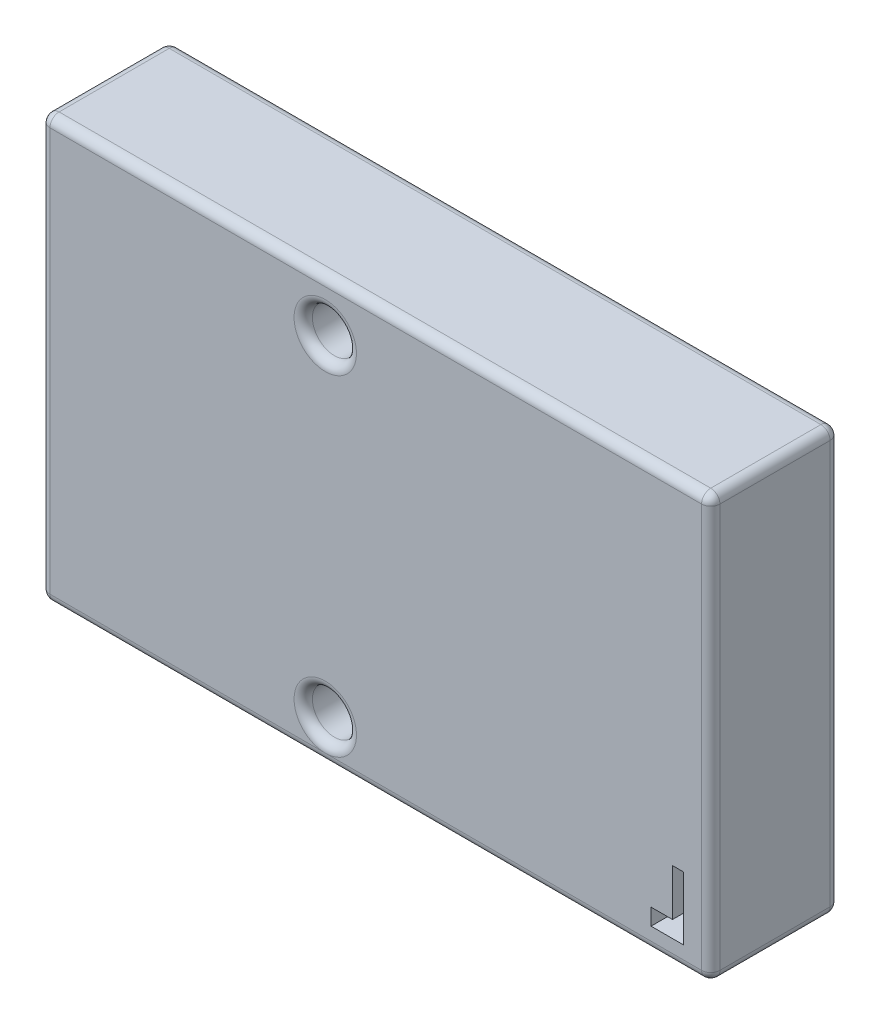
SolidWorks part; units mm, degrees
ref_plane "Front Plane" through (0, 0, 0) normal (0, 0, 1) x (1, 0, 0)
ref_plane "Top Plane" through (0, 0, 0) normal (0, 1, 0) x (1, 0, 0)
ref_plane "Right Plane" through (0, 0, 0) normal (1, 0, 0) x (0, 0, -1)
sketch "Sketch1" plane through (0, 0, 0) normal (0, 1, 0) x (1, 0, 0)
  line L0 (0, 0) -> (36.5, 0)
  line L1 (36.5, 0) -> (36.5, -7)
  line L2 (36.5, -7) -> (0, -7)
  line L3 (0, -7) -> (0, 0)
  dimension "D1" = 36.5
  dimension "D2" = 7
extrude "Boss-Extrude1" add sketch "Sketch1" along normal blind 23
sketch "Sketch2" plane through (0, 0, 0) normal (0, -1, 0) x (1, 0, 0)
  line L0 (36.5, 0) -> (0, 0) construction
  line L1 (36.5, 7) -> (36.5, 0) construction
  line L2 (0, 0) -> (0, 7) construction
  circle A0 centre (8, 3) radius 1.375
  circle A1 centre (28.5, 3) radius 1.375
  dimension "D3" = 2.75
  dimension "D1" = 3
  dimension "D4" = 8
  dimension "D5" = 8
extrude "Cut-Extrude1" cut sketch "Sketch2" against normal blind 8.5
sketch "Sketch4" plane through (0, 0, 0) normal (0, 0, -1) x (-1, 0, 0)
  line L0 (-36.5, 0) -> (0, 0) construction
  line L2 (-8, 8.5) -> (-8, 0) construction
  circle A0 centre (-15.5, 2.2) radius 1.2
  circle A1 centre (-15.5, 20.2) radius 1.2
  dimension "D1" = 2.4
  dimension "D4" = 18
  dimension "D2" = 2.2
  dimension "D3" = 7.5
extrude "Cut-Extrude2" cut sketch "Sketch4" against normal blind 7
fillet "Fillet1" radius 0.5 18 edges at (18.25, 23, 0) (14.3, 20.2, 0) (14.3, 2.2, 0) (0, 11.5, 0) (0, 23, 3.5) (36.5, 23, 3.5) (36.5, 11.5, 0) (0, 11.5, 7) (18.25, 23, 7) (36.5, 11.5, 7) (14.3, 20.2, 7) (14.3, 2.2, 7) (18.25, 0, 7) (36.5, 0, 3.5) (18.25, 0, 0) (0, 0, 3.5) (28.5, 0, 1.625) (8, 0, 1.625)
sketch "Sketch5" plane through (0, 0, 0) normal (0, 0, -1) x (-1, 0, 0)
  line L0 (-35.0148, 4.6521) -> (-35.0148, 1.2093)
  line L1 (-35.0148, 1.2093) -> (-33.2485, 1.2093)
  line L2 (-33.2485, 1.2093) -> (-33.2485, 2.1075)
  line L3 (-33.2485, 2.1075) -> (-34.416, 2.1075)
  line L4 (-34.416, 2.1075) -> (-34.416, 4.6521)
  line L5 (-34.416, 4.6521) -> (-35.0148, 4.6521)
  line L6 (-36, 0.5) -> (-15.5, 0.5) construction
  line L7 (-36, 22.5) -> (-36, 0.5) construction
  dimension "D1" = 1.7663
  dimension "D2" = 0.5987
  dimension "D3" = 3.4428
  dimension "D4" = 2.5447
  dimension "D5" = 0.7093
  dimension "D6" = 0.9852
extrude "Cut-Extrude3" cut sketch "Sketch5" against normal through all
